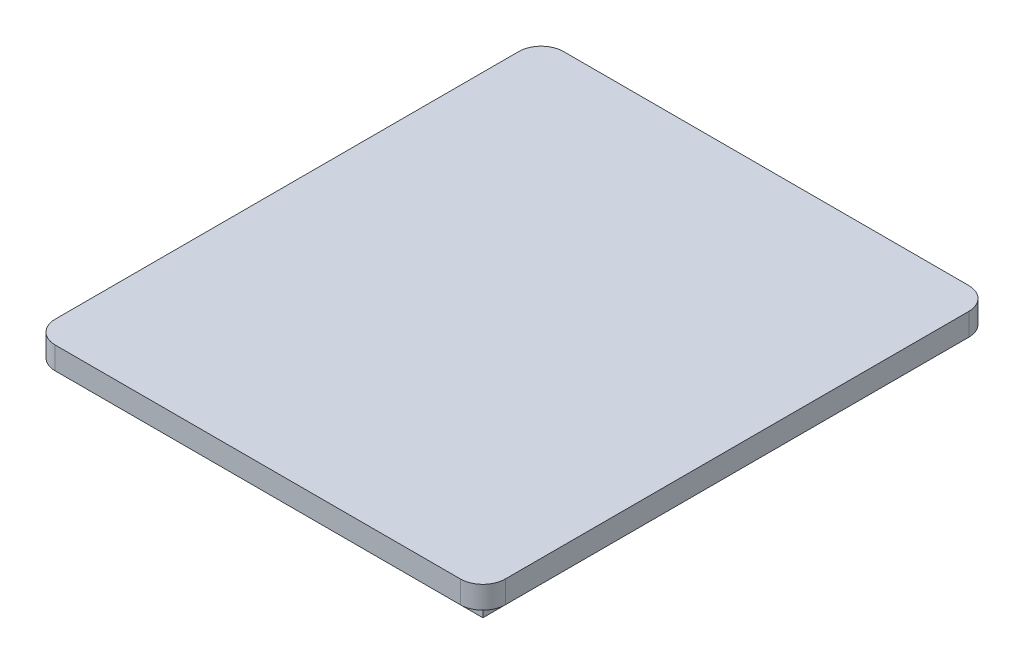
SolidWorks part; units mm, degrees
ref_plane "Front Plane" through (0, 0, 0) normal (0, 0, 1) x (1, 0, 0)
ref_plane "Top Plane" through (0, 0, 0) normal (0, 1, 0) x (1, 0, 0)
ref_plane "Right Plane" through (0, 0, 0) normal (1, 0, 0) x (0, 0, -1)
sketch "Sketch1" plane through (0, 0, 0) normal (0, 1, 0) x (1, 0, 0)
  line L1 (-50.2, -56.7) -> (50.2, -56.7)
  line L2 (-50.2, -56.7) -> (-50.2, 56.7)
  line L3 (-50.2, 56.7) -> (50.2, 56.7)
  line L4 (50.2, -56.7) -> (50.2, 56.7)
  line L5 (-50.2, -56.7) -> (50.2, 56.7) construction
  line L6 (-50.2, 56.7) -> (50.2, -56.7) construction
  point P0 (0, 0)
  dimension "D1" = 100.4
  dimension "D2" = 113.4
extrude "Boss-Extrude1" add sketch "Sketch1" along normal blind 5
sketch "Sketch2" plane through (0, 0, 0) normal (0, -1, 0) x (1, 0, 0)
  line L0 (50.2, 56.7) -> (50.2, -56.7) construction
  line L1 (-45.2, -51.7) -> (45.2, -51.7)
  line L2 (-45.2, -51.7) -> (-45.2, 51.7)
  line L3 (-45.2, 51.7) -> (45.2, 51.7)
  line L4 (45.2, -51.7) -> (45.2, 51.7)
  line L5 (-45.2, -51.7) -> (45.2, 51.7) construction
  line L6 (-45.2, 51.7) -> (45.2, -51.7) construction
  line L8 (-50.2, 56.7) -> (50.2, 56.7) construction
  point P0 (0, 0)
  dimension "D1" = 5
  dimension "D2" = 5
extrude "Boss-Extrude2" add sketch "Sketch2" along normal blind 5
fillet "Fillet1" radius 5 4 edges at (-50.2, 2.5, -56.7) (50.2, 2.5, -56.7) (50.2, 2.5, 56.7) (-50.2, 2.5, 56.7)
sketch "Sketch3" plane through (0, 5, 0) normal (0, 1, 0) x (1, 0, 0)
  line L0 (45.2, 56.7) -> (-45.2, 56.7) construction
  line L1 (-50.2, 51.7) -> (-50.2, -51.7) construction
  circle A0 centre (-35.2, 36.65) radius 1.5
  circle A1 centre (-35.2, -36.65) radius 1.5
  circle A2 centre (35.2, 36.65) radius 1.5
  circle A3 centre (35.2, -36.65) radius 1.5
  dimension "D1" = 73.3
  dimension "D5" = 20.05
  dimension "D2" = 73.3
  dimension "D3" = 70.4
  dimension "D4" = 70.4
  dimension "D6" = 15
